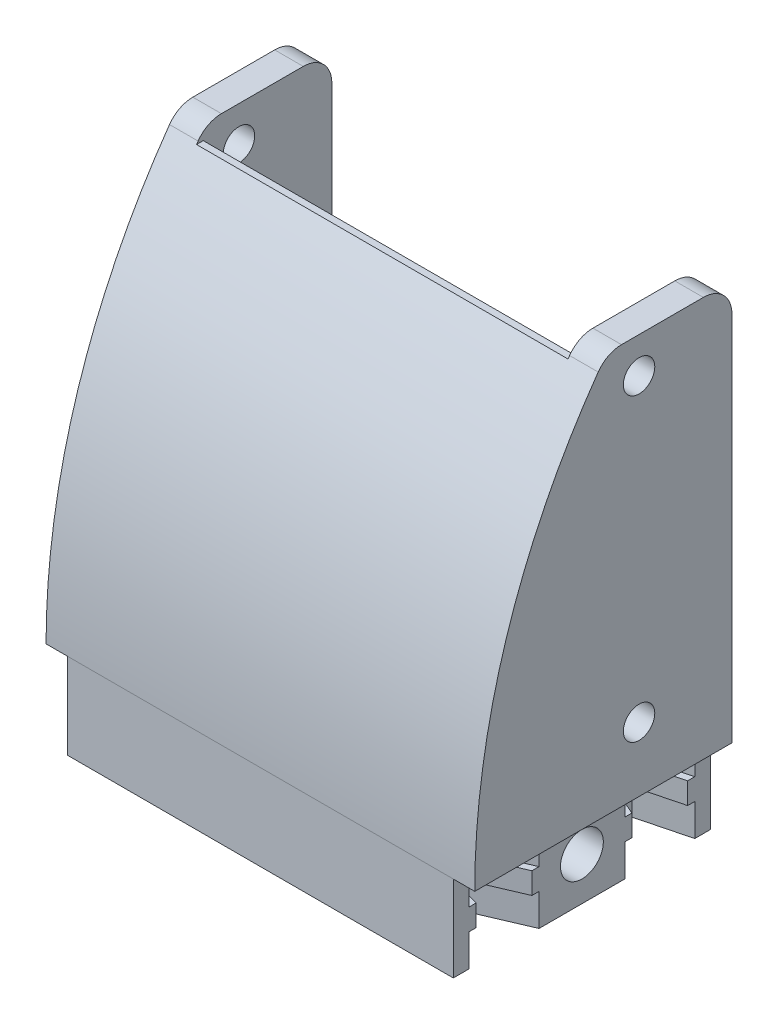
SolidWorks part; units mm, degrees
material "ABS"
ref_plane "正面" through (0, 0, 0) normal (0, 0, 1) x (1, 0, 0)
ref_plane "平面" through (0, 0, 0) normal (0, 1, 0) x (1, 0, 0)
ref_plane "右側面" through (0, 0, 0) normal (1, 0, 0) x (0, 0, -1)
sketch "ｽｹｯﾁ1" plane through (0, 0, 0) normal (1, 0, 0) x (0, 0, -1)
  line L0 (9, 31) -> (0.2508, 31)
  line L2 (-9, 3) -> (-9, -3)
  line L3 (-9, -3) -> (9, -3)
  line L4 (9, 31) -> (9, -3)
  arc A0 (-9, 3) -> (0.2508, 31) centre (38, 3) cw
  point P0 (0, 0)
  point P8 (0, -3)
  point P10 (-9, 0)
  dimension "D6" = 47
  dimension "D1" = 18
  dimension "D2" = 0
  dimension "D3" = 6
  dimension "D4" = 0
  dimension "D5" = 34
extrude "ﾎﾞｽ - 押し出し1" add sketch "ｽｹｯﾁ1" along normal mid plane 30
sketch "ｽｹｯﾁ2" plane through (0, 0, -9) normal (0, 0, -1) x (-1, 0, 0)
  line L0 (-15, 31) -> (15, 31) construction
  line L1 (-13, 31) -> (13, 31)
  line L2 (-13, 31) -> (-13, 5)
  line L3 (-13, 5) -> (13, 5)
  line L4 (13, 31) -> (13, 5)
  line L5 (-13, 31) -> (13, 5) construction
  line L6 (-13, 5) -> (13, 31) construction
  line L7 (-15, -3) -> (-15, 31) construction
  line L8 (15, -3) -> (15, 31) construction
  line L9 (-15, -3) -> (15, -3) construction
  point P4 (0, 18)
  dimension "D1" = 2
  dimension "D2" = 2
  dimension "D3" = 8
extrude "ｶｯﾄ - 押し出し1" cut sketch "ｽｹｯﾁ2" against normal blind 9
fillet "ﾌｨﾚｯﾄ1" radius 2 3 edges at (-14, 31, -0.2508) (14, 31, -9) (-14, 31, -9)
sketch "ｽｹｯﾁ3" plane through (0, 5, 0) normal (0, 1, 0) x (1, 0, 0)
  line L0 (13, 9) -> (-13, 9) construction
  line L1 (-8.75, 9) -> (8.75, 9)
  line L2 (-8.75, 9) -> (-8.75, 6)
  line L3 (-8.75, 6) -> (8.75, 6)
  line L4 (8.75, 9) -> (8.75, 6)
  line L5 (-8.75, 9) -> (8.75, 6) construction
  line L6 (-8.75, 6) -> (8.75, 9) construction
  point P4 (0, 7.5)
  dimension "D1" = 0
  dimension "D2" = 17.5
  dimension "D3" = 3
extrude "ｶｯﾄ - 押し出し2" cut sketch "ｽｹｯﾁ3" against normal up to next
sketch "ｽｹｯﾁ4" plane through (15, 0, 0) normal (1, 0, 0) x (0, 0, -1)
  circle A0 centre (0, 0) radius 1.5
  dimension "D1" = 3
extrude "ｶｯﾄ - 押し出し3" cut sketch "ｽｹｯﾁ4" against normal through all
sketch "ｽｹｯﾁ6" plane through (0, 0, 9) normal (0, 0, 1) x (1, 0, 0)
  line L0 (15, -3) -> (-15, -3) construction
  line L1 (-15, 3) -> (-13.5, 3)
  line L2 (-15, 3) -> (-15, -3)
  line L3 (-15, -3) -> (-13.5, -3)
  line L4 (-13.5, 3) -> (-13.5, -3)
  line L5 (-15, 3) -> (-13.5, -3) construction
  line L6 (-15, -3) -> (-13.5, 3) construction
  line L7 (15, 3) -> (-15, 3) construction
  line L8 (15, -3) -> (13.5, -3)
  line L9 (15, -3) -> (15, 3)
  line L10 (15, 3) -> (13.5, 3)
  line L11 (13.5, -3) -> (13.5, 3)
  line L12 (15, -3) -> (13.5, 3) construction
  line L13 (15, 3) -> (13.5, -3) construction
  point P4 (-14.25, 0)
  point P12 (14.25, 0)
  dimension "D1" = 27
extrude "ｶｯﾄ - 押し出し5" cut sketch "ｽｹｯﾁ6" against normal through all
sketch "ｽｹｯﾁ5" plane through (0, -3, 0) normal (0, -1, 0) x (1, 0, 0)
  line L0 (13.5, -3) -> (10, -4.5)
  line L2 (10, -4.5) -> (10, -7)
  line L3 (10, -7) -> (13.5, -7.9)
  line L4 (13.5, -3) -> (13.5, -7.9)
  line L5 (13.5, -9) -> (13.5, 9) construction
  dimension "D1" = 3.5
  dimension "D2" = 7
  dimension "D3" = 2.5
  dimension "D4" = 7.9
  dimension "D5" = 3
extrude "ｶｯﾄ - 押し出し4" cut sketch "ｽｹｯﾁ5" against normal blind 6
mirror "ﾐﾗｰ1" about plane through (0, 0, 0) normal (0, 0, 1) of "ｶｯﾄ - 押し出し4"
sketch "ｽｹｯﾁ7" plane through (0, -3, 0) normal (0, -1, 0) x (1, 0, 0)
  line L1 (-11.25, 2.5) -> (11.25, 2.5)
  line L2 (-11.25, 2.5) -> (-11.25, -2.5)
  line L3 (-11.25, -2.5) -> (11.25, -2.5)
  line L4 (11.25, 2.5) -> (11.25, -2.5)
  line L5 (-11.25, 2.5) -> (11.25, -2.5) construction
  line L6 (-11.25, -2.5) -> (11.25, 2.5) construction
  point P0 (0, 0)
extrude "ﾎﾞｽ - 押し出し2" add sketch "ｽｹｯﾁ7" along normal blind 0.5
fillet "ﾌｨﾚｯﾄ2" radius 0.5 4 edges at (0, -3.5, -2.5) (11.25, -3.5, 0) (0, -3.5, 2.5) (-11.25, -3.5, 0)
hole_wizard "Ø2.2 (2.2) 直径の穴1" positions "ｽｹｯﾁ8" profile "ｽｹｯﾁ9" hole size "Ø2.2" standard "JIS" end condition up to next
sketch "ｽｹｯﾁ8" plane through (15, 0, 0) normal (1, 0, 0) x (0, 0, -1)
  line L0 (2.5, 28.5) -> (2.5, 7.5) construction
  line L2 (9, 3) -> (9, 29) construction
  line L3 (7, 31) -> (1.2713, 31) construction
  point P0 (2.5, 28.5)
  point P2 (2.5, 7.5)
  dimension "D1" = 6.5
  dimension "D2" = 21
  dimension "D3" = 2.5
sketch "ｽｹｯﾁ9" plane through (15, 28.5, -2.5) normal (0, 1, 0) x (0, 0, -1)
  line L0 (0, 0) -> (0, 2)
  line L1 (0, 2) -> (1.1, 2)
  line L2 (1.1, 2) -> (1.1, 0)
  line L5 (1.1, 0) -> (0, 0)
  line L11 (0, -6.35) -> (0, 107.95) construction
  dimension "通し穴の直径" = 2.2
  dimension "通し穴の深さ" = 2
mirror "ﾐﾗｰ2" about plane through (0, 0, 0) normal (1, 0, 0) of "Ø2.2 (2.2) 直径の穴1", "ﾐﾗｰ1", "ｶｯﾄ - 押し出し4"
sketch "ｽｹｯﾁ10" plane through (0, 0, 0) normal (0, 0, -1) x (-1, 0, 0)
  line L0 (-13, 30.544) -> (-13, 5) construction
  line L1 (-13, 30) -> (13, 30)
  line L2 (-13, 30) -> (-13, 33)
  line L3 (-13, 33) -> (13, 33)
  line L4 (13, 30) -> (13, 33)
  line L5 (-13, 30) -> (13, 33) construction
  line L6 (-13, 33) -> (13, 30) construction
  line L7 (-13, 5) -> (13, 5) construction
  line L8 (13, 5) -> (13, 29) construction
  point P4 (0, 31.5)
  dimension "D1" = 25
  dimension "D2" = 3
extrude "ｶｯﾄ - 押し出し6" cut sketch "ｽｹｯﾁ10" against normal through all
ref_plane "平面1" through (0, 0, 0) normal (0, -1, 0) x (-1, 0, 0)
sketch "ｽｹｯﾁ12" plane through (0, 0, 0) normal (0, -1, 0) x (-1, 0, 0)
  line L0 (13.5, -7.9) -> (10, -7)
  line L1 (10, -7) -> (10, -6.5)
  line L2 (10, -4.5) -> (10, -7) construction
  line L3 (10, -6.5) -> (13.5, -7.4)
  line L4 (13.5, -7.4) -> (13.5, -7.9)
  line L5 (10, -4.5) -> (10, -5)
  line L6 (10, -5) -> (13.5, -3.5)
  line L7 (13.5, -3.5) -> (13.5, -3)
  line L8 (13.5, -3) -> (10, -4.5) construction
  line L9 (13.5, -3) -> (10, -4.5)
  dimension "D1" = 0.5
extrude "ﾎﾞｽ - 押し出し3" add sketch "ｽｹｯﾁ12" along normal mid plane 1.5
mirror "ﾐﾗｰ3" about plane through (0, 0, 0) normal (0, 0, 1) of "ﾎﾞｽ - 押し出し3"
mirror "ﾐﾗｰ4" about plane through (0, 0, 0) normal (1, 0, 0) of "ﾐﾗｰ3", "ﾎﾞｽ - 押し出し3"
